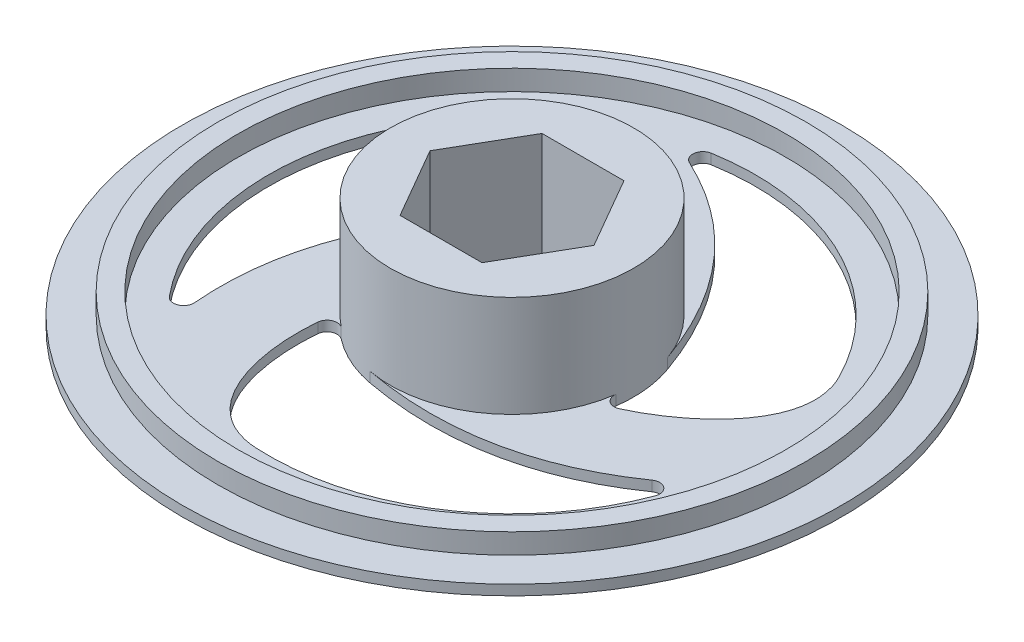
SolidWorks part; units mm, degrees
ref_plane "Alzado" through (0, 0, 0) normal (0, 0, 1) x (1, 0, 0)
ref_plane "Planta" through (0, 0, 0) normal (0, 1, 0) x (1, 0, 0)
ref_plane "Vista lateral" through (0, 0, 0) normal (1, 0, 0) x (0, 0, -1)
sketch "Croquis1" plane through (0, 0, 0) normal (0, 1, 0) x (1, 0, 0)
  circle A12 centre (0, 0) radius 32.5
  dimension "D1" = 65
extrude "Saliente-Extruir1" add sketch "Croquis1" along normal blind 1
sketch "Croquis2" plane through (0, 1, 0) normal (0, 1, 0) x (1, 0, 0)
  circle A0 centre (0, 0) radius 12
  dimension "D1" = 24
extrude "Saliente-Extruir2" add sketch "Croquis2" along normal blind 10
sketch "Croquis3" plane through (0, 0, 0) normal (0, 1, 0) x (1, 0, 0)
  line L0 (0, 0) -> (14.077, 0) construction
  line L1 (4.0415, -7) -> (8.0829, 0)
  line L2 (8.0829, 0) -> (4.0415, 7)
  line L3 (4.0415, 7) -> (-4.0415, 7)
  line L4 (-4.0415, 7) -> (-8.0829, 0)
  line L5 (-8.0829, 0) -> (-4.0415, -7)
  line L6 (-4.0415, -7) -> (4.0415, -7)
  circle A0 centre (0, 0) radius 7 construction
  point P1 (7.9303, -0.787)
  point P10 (7.864, 0)
  dimension "D1" = 14
extrude "Cortar-Extruir1" cut sketch "Croquis3" along normal through all both and the other way through all
sketch "Croquis4" plane through (0, 1, 0) normal (0, 1, 0) x (1, 0, 0)
  circle A0 centre (0, 0) radius 27
  circle A1 centre (0, 0) radius 29
  dimension "D1" = 54
  dimension "D2" = 58
extrude "Saliente-Extruir3" add sketch "Croquis4" along normal blind 2
sketch "Croquis5" plane through (0, 1, 0) normal (0, 1, 0) x (1, 0, 0)
  arc A0 (-20.1246, 13.0767) -> (-16.3192, -17.5978) centre (0, 0) ccw
  circle A1 centre (0, 0) radius 12 construction
  circle A2 centre (0, 0) radius 12 construction
  arc A3 (-8.6949, -8.2704) -> (-2.1879, -11.7989) centre (0, 0) ccw
  arc A4 (-0.5801, 11.986) -> (-9.1242, 7.7942) centre (0, 0) ccw
  arc A5 (11.5098, -3.3948) -> (11.3121, 4.0047) centre (0, 0) ccw
  arc A6 (-1.2625, -23.9668) -> (23.3998, -5.3339) centre (0, 0) ccw
  arc A7 (21.3871, 10.8901) -> (-7.0806, 22.9318) centre (0, 0) ccw
  spline S0 degree 3 poles (-0.5801, 11.986) (-4.8674, 14.9037) (-15.6964, 19.8915) (-20.1246, 13.0767) knots 0 0 0 0 1 1 1 1
  spline S1 degree 2 poles (-16.3192, -17.5978) (-18.8195, -3.5555) (-9.1242, 7.7942) knots 0 0 0 1 1 1
  spline S2 degree 2 poles (-7.0806, 22.9318) (6.3306, 18.076) (11.3121, 4.0047) knots 0 0 0 1 1 1
  spline S3 degree 3 poles (11.5098, -3.3948) (16.2095, -1.9284) (24.8444, 4.1003) (21.3871, 10.8901) knots 0 0 0 0 1 1 1 1
  spline S4 degree 2 poles (23.3998, -5.3339) (12.489, -14.5204) (-2.1879, -11.7989) knots 0 0 0 1 1 1
  spline S5 degree 3 poles (-8.6949, -8.2704) (-9.7748, -13.0737) (-8.8712, -23.566) (-1.2625, -23.9668) knots 0 0 0 0 1 1 1 1
  point P13 (-0.5801, 11.986)
  point P14 (-7.5792, 15.4436)
  point P28 (0, 0)
  dimension "D1" = 48
extrude "Cortar-Extruir2" cut sketch "Croquis5" against normal through all both and the other way through all
fillet "Redondeo1" radius 1 9 edges at (-7.0806, 0.5, -22.9318) (11.5098, 0.5, 3.3948) (21.3871, 0.5, -10.8901) (23.3998, 0.5, 5.3339) (-8.6949, 0.5, 8.2704) (-1.2625, 0.5, 23.9668) (-16.3192, 0.5, 17.5978) (-0.5801, 0.5, -11.986) (-20.1246, 0.5, -13.0767)
